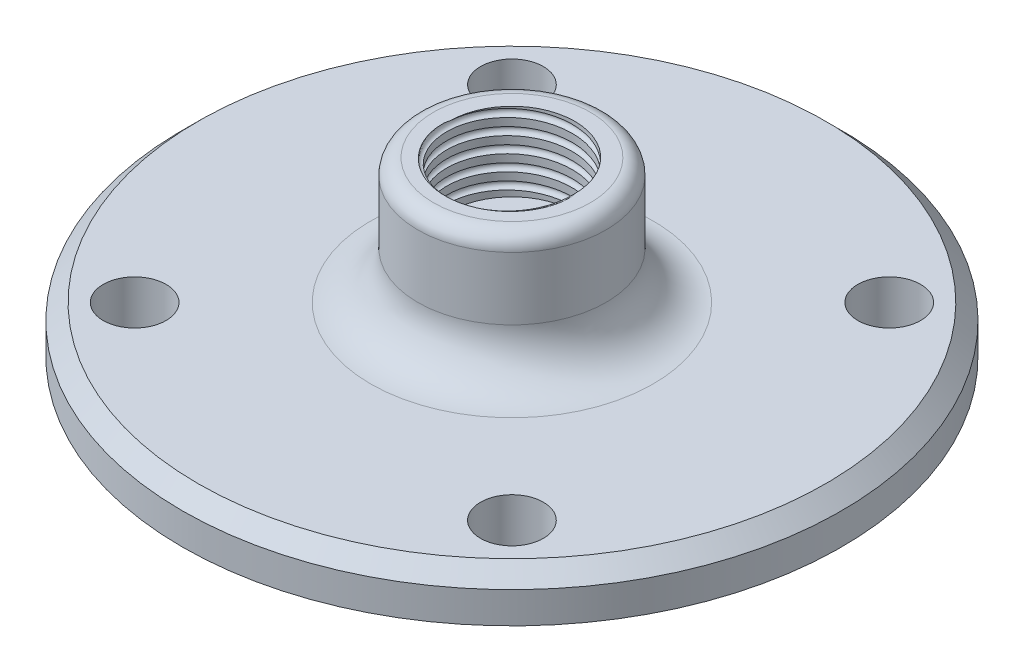
SolidWorks part; units mm, degrees
note: The reader was unsure of these and kept them because the rebuilt part matched: shared geometry of "Sketch1<3>", "Sketch1<4>", "Sketch1<5>".
ref_plane "Front Plane" through (0, 0, 0) normal (0, 0, 1) x (1, 0, 0)
ref_plane "Top Plane" through (0, 0, 0) normal (0, 1, 0) x (1, 0, 0)
ref_plane "Right Plane" through (0, 0, 0) normal (1, 0, 0) x (0, 0, -1)
sketch "Sketch1" plane through (0, 0, 0) normal (0, 1, 0) x (1, 0, 0)
  circle A0 centre (0, 0) radius 21
  circle A2 centre (-12.0208, 12.0208) radius 2
  circle A3 centre (12.0208, 12.0208) radius 2
  circle A4 centre (12.0208, -12.0208) radius 2
  circle A5 centre (-12.0208, -12.0208) radius 2
  circle A6 centre (0, 0) radius 6
  circle A7 centre (0, 0) radius 4
  circle A8 centre (0, 0) radius 2.5
  point P15 (0, 0)
  dimension "D2" = 4
extrude "Boss-Extrude1" add sketch "Sketch1" along normal blind 3 contours A0 A6 A5 A4 A3 A2
extrude "Boss-Extrude2" add sketch "Sketch1<3>" along normal blind 11 contours A6 A7
sketch "Sketch1<3>" plane through (0, 0, 0) normal (0, 1, 0) x (1, 0, 0) same geometry as "Sketch1"
extrude "Boss-Extrude3" add sketch "Sketch1<4>" along normal blind 6 contours A7 A8
sketch "Sketch1<4>" plane through (0, 0, 0) normal (0, 1, 0) x (1, 0, 0) same geometry as "Sketch1"
fillet "Fillet1" radius 3 1 edges at (0, 3, 6)
sketch "Sketch2" plane through (0, 0, 0) normal (0, -1, 0) x (1, 0, 0)
  circle A0 centre (0, 0) radius 12
extrude "Boss-Extrude4" add sketch "Sketch2" along normal blind 1
extrude "Cut-Extrude1" cut sketch "Sketch1<5>" against normal through all contours A8
sketch "Sketch1<5>" plane through (0, 0, 0) normal (0, 1, 0) x (1, 0, 0) same geometry as "Sketch1"
fillet "Fillet2" radius 1 1 edges at (0, 11, 6)
chamfer "Chamfer1" distance 1 angle 45 1 edges at (0, 3, 21)
sketch "Sketch4" plane through (0, 11, 0) normal (0, 1, 0) x (1, 0, 0)
  circle A0 centre (0, 0) radius 4 construction
  circle A1 centre (0, 0) radius 4
curve "Helix/Spiral1" pitch 1 height 5 turns 5
sketch "Sketch5" plane through (0, 0, 0) normal (1, 0, 0) x (0, 0, -1)
  circle A0 centre (-4, 11) radius 0.25
sweep "Cut-Sweep2" cut profiles "Sketch5" path "Helix/Spiral1" align with end faces yes
